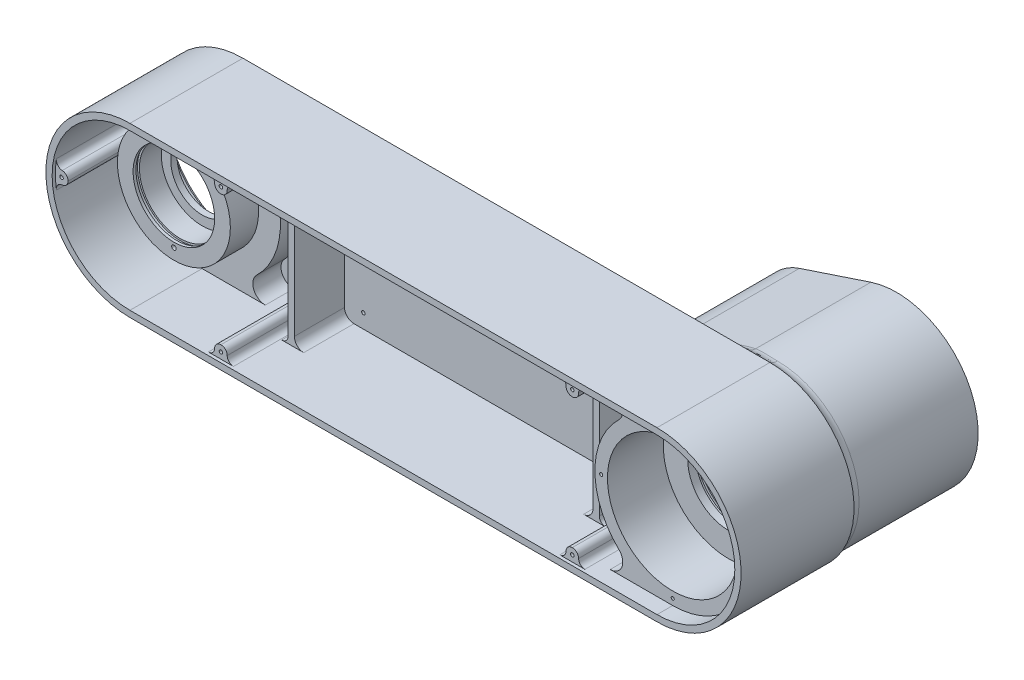
SolidWorks part; units mm, degrees
note: '?' marks a value the reader was unsure of. The reader was unsure of these and kept them because the rebuilt part matched: shared geometry of "Sketch1<2>", "Sketch5<2>", "Sketch20<2>".
ref_plane "Front Plane" through (0, 0, 0) normal (0, 0, 1) x (1, 0, 0)
ref_plane "Top Plane" through (0, 0, 0) normal (0, 1, 0) x (1, 0, 0)
ref_plane "Right Plane" through (0, 0, 0) normal (1, 0, 0) x (0, 0, -1)
sketch "Sketch1" plane through (0, 0, 0) normal (0, 0, 1) x (1, 0, 0)
  line L0 (0, 42.545) -> (266.7, 42.545)
  line L1 (0, -42.545) -> (266.7, -42.545)
  line L2 (0, 39.37) -> (266.7, 39.37)
  line L3 (0, -39.37) -> (266.7, -39.37)
  line L4 (266.7, 0) -> (0, 0) construction
  line L5 (133.35, 39.37) -> (133.35, -39.37) construction
  arc A0 (0, 42.545) -> (0, -42.545) centre (0, 0) ccw
  arc A1 (266.7, 42.545) -> (266.7, -42.545) centre (266.7, 0) cw
  arc A2 (266.7, 39.37) -> (266.7, -39.37) centre (266.7, 0) cw
  arc A3 (0, 39.37) -> (0, -39.37) centre (0, 0) ccw
  dimension "D1" = 85.09
  dimension "D2" = 266.7
  dimension "D3" = 3.175
extrude "Boss-Extrude1" add sketch "Sketch1" along normal blind 50.8
extrude "Boss-Extrude2" add sketch "Sketch1<2>" against normal blind 6.35 contours L2 A3 L3 A2 | A1 L0 A0 L1 A3 L2 A2 L3
sketch "Sketch1<2>" plane through (0, 0, 0) normal (0, 0, 1) x (1, 0, 0) same geometry as "Sketch1"
ref_plane "Plane1" through (0, 0, -6.35) normal (0, 0, -1) x (-1, 0, 0)
ref_plane "Plane2" through (0, 0, 0) normal (0, 0, 1) x (1, 0, 0)
sketch "Sketch3" plane through (0, 0, -6.35) normal (0, 0, -1) x (-1, 0, 0)
  circle A0 centre (0, 0) radius 38.1
  dimension "D1" = 76.2
extrude "Cut-Extrude1" cut sketch "Sketch3" against normal blind 5.08
ref_axis "Axis1" through (0, 0, -1.27) along (0, 0, -1)?
sketch "Sketch4" plane through (0, 0, 0) normal (0, 0, 1) x (1, 0, 0)
  circle A0 centre (0, 0) radius 31.75
  dimension "D1" = 63.5
extrude "Cut-Extrude2" cut sketch "Sketch4" against normal up to surface (6.35 mm away) contours A0 up to plane "Plane1"
ref_plane "Plane3" through (0, 0, 50.8) normal (0, 0, 1) x (1, 0, 0)
sketch "Sketch15" plane through (0, 0, 0) normal (0, 0, 1) x (1, 0, 0)
  circle A0 centre (0, 0) radius 31.75
  circle A1 centre (0, 0) radius 39.624
  arc A3 (0, 39.37) -> (0, -39.37) centre (0, 0) ccw construction
  dimension "D1" = 63.5
  dimension "D2" = 0.254
extrude "Boss-Extrude6" add sketch "Sketch15" along normal blind 11.0975
sketch "Sketch5" plane through (0, 0, -6.35) normal (0, 0, -1) x (-1, 0, 0)
  line L0 (0, 0) -> (-253.1261, -84.0003) construction
  line L1 (0, 0) -> (-266.7, 0) construction
  line L2 (-253.1261, -84.0003) -> (-266.7, 0) construction
  line L3 (-217.5391, -27.1742) -> (-253.6999, -39.1743)
  line L4 (-253.1261, 84.0003) -> (-266.7, 0) construction
  line L5 (-217.5391, 27.1742) -> (-253.6999, 39.1743)
  line L6 (0, 0) -> (-253.1261, 84.0003) construction
  line L7 (-218.5391, -24.1608) -> (-254.7, -36.1609)
  line L8 (-218.5391, 24.1608) -> (-254.7, 36.1609)
  arc A0 (-254.7, 36.1609) -> (-254.7, -36.1609) centre (-266.7, 0) ccw
  arc A2 (-253.6999, 39.1743) -> (-253.6999, -39.1743) centre (-266.7, 0) ccw
  arc A3 (-217.5391, -27.1742) -> (-217.5391, 27.1742) centre (-226.5569, 0) ccw
  arc A4 (-218.5391, -24.1608) -> (-218.5391, 24.1608) centre (-226.5569, 0) ccw
  dimension "D1" = 266.7
  dimension "D2" = 82.55
  dimension "D3" = 266.7
  dimension "D4" = 85.09
  dimension "D5" = 38.1
  dimension "D6" = 3.175
extrude "Boss-Extrude3" add sketch "Sketch5" along normal up to surface (64.07 mm away)
extrude "Boss-Extrude4" add sketch "Sketch5<2>" along normal up to surface (13.27 mm away) contours L7 A4 L8 A0
sketch "Sketch5<2>" plane through (0, 0, -6.35) normal (0, 0, -1) x (-1, 0, 0) same geometry as "Sketch5"
ref_plane "Plane4" through (0, 0, -19.62) normal (0, 0, -1) x (-1, 0, 0)
ref_axis "Axis5" through (266.7, 0, 50.8) along (0, 0, -1)?
sketch "Sketch20" plane through (0, 0, 0) normal (0, 0, 1) x (1, 0, 0)
  circle A0 centre (266.7, 0) radius 33.02
  circle A1 centre (266.7, 0) radius 39.37
  arc A2 (266.7, -39.37) -> (266.7, 39.37) centre (266.7, 0) ccw construction
  dimension "D1" = 6.35
extrude "Boss-Extrude9" add sketch "Sketch20" along normal blind 42.8625
extrude "Boss-Extrude10" add sketch "Sketch20<2>" along normal blind 14.59 contours A0
sketch "Sketch20<2>" plane through (0, 0, 0) normal (0, 0, 1) x (1, 0, 0) same geometry as "Sketch20"
sketch "Sketch23" plane through (0, 0, -19.62) normal (0, 0, -1) x (-1, 0, 0)
  circle A0 centre (-266.7, 0) radius 20.6375
  dimension "D1" = 41.275
extrude "Cut-Extrude6" cut sketch "Sketch23" against normal blind 28.575 from offset 6.35 offset against normal yes
sketch "Sketch24" plane through (0, 0, -19.62) normal (0, 0, -1) x (-1, 0, 0)
  circle A0 centre (-266.7, 0) radius 21.9075
  dimension "D1" = 43.815
extrude "Cut-Extrude7" cut sketch "Sketch24" against normal blind 1.7272 from offset 28.575 offset against normal yes
sketch "Sketch8" plane through (0, 0, 0) normal (0, 0, 1) x (1, 0, 0)
  circle A0 centre (266.7, 0) radius 14.2875
  arc A1 (266.7, -39.37) -> (266.7, 39.37) centre (266.7, 0) ccw construction
  dimension "D1" = 28.575
extrude "Cut-Extrude3" cut sketch "Sketch8" against normal up to surface (19.62 mm away) up to plane "Plane4"
ref_axis "Axis2" through (266.7, 0, -19.62) along (0, 0, 1)?
ref_axis "Axis3" through (266.7, 0, 0) along (-1, 0, 0)?
ref_axis "Axis4" through (133.35, 39.37, 0) along (0, -1, 0)?
sketch "Sketch9" plane through (0, 0, 0) normal (0, 0, 1) x (1, 0, 0)
  line L0 (64.135, 39.37) -> (202.565, 39.37)
  line L1 (202.565, 39.37) -> (202.565, 25.4)
  line L2 (202.565, 25.4) -> (64.135, 25.4)
  line L3 (64.135, 25.4) -> (64.135, 39.37)
  line L4 (64.135, -25.4) -> (64.135, -39.37)
  line L5 (64.135, -39.37) -> (202.565, -39.37)
  line L6 (202.565, -39.37) -> (202.565, -25.4)
  line L7 (202.565, -25.4) -> (64.135, -25.4)
  line L8 (64.135, 25.4) -> (64.135, 0) construction
  line L9 (202.565, 25.4) -> (202.565, -25.4) construction
  line L10 (64.135, 0) -> (64.135, -25.4) construction
  line L11 (266.7, 0) -> (0, 0) construction
  line L12 (133.35, 12.7) -> (133.35, -12.7) construction
  line L13 (133.35, 39.37) -> (133.35, -39.37) construction
  line L14 (64.135, 0) -> (0, 0) construction
  line L15 (202.565, 0) -> (266.7, 0) construction
  point P11 (199.39, 32.1818)
  point P16 (133.35, 0)
  point P20 (67.31, 32.1818)
  point P21 (67.31, -32.1818)
  point P22 (199.39, -32.1818)
  dimension "D1" = 78.74
  dimension "D2" = 25.4
  dimension "D3" = 3.175
  dimension "D4" = 138.43
  dimension "D5" = 25.4
  dimension "D6" = 32.1818
  dimension "D7" = 3.175
sketch "Sketch17" plane through (0, 0, 11.0975) normal (0, 0, 1) x (1, 0, 0)
  circle A0 centre (0, 0) radius 15.875
  circle A1 centre (0, 0) radius 39.624
  circle A2 centre (0, 0) radius 39.624 construction
  dimension "D1" = 31.75
extrude "Boss-Extrude7" add sketch "Sketch17" along normal blind 3.175
sketch "Sketch18" plane through (0, 0, 14.2725) normal (0, 0, 1) x (1, 0, 0)
  circle A0 centre (0, 0) radius 20.6375
  circle A1 centre (0, 0) radius 28.575
  dimension "D1" = 41.275
  dimension "D2" = 57.15
extrude "Boss-Extrude8" add sketch "Sketch18" along normal blind 14.2875
ref_plane "Plane7" through (0, 0, 14.2725) normal (0, 0, 1) x (1, 0, 0)
sketch "Sketch19" plane through (0, 0, 14.2725) normal (0, 0, 1) x (1, 0, 0)
  circle A0 centre (0, 0) radius 20.6375
  circle A1 centre (0, 0) radius 21.59
  dimension "D1" = 41.275
  dimension "D2" = 43.18
extrude "Cut-Extrude5" cut sketch "Sketch19" along normal blind 1.7272 from offset 11.1125
fillet "Fillet2" radius 6.35 2 edges at (4.4793, 39.37, 7.1363) (4.4793, -39.37, 7.1363)
sketch "Sketch25" plane through (0, 0, 42.8625) normal (0, 0, 1) x (1, 0, 0)
  line L0 (230.505, 0) -> (266.7, 0) construction
  circle A0 centre (230.505, 0) radius 0.7938
  circle A1 centre (266.7, 36.195) radius 0.7938
  circle A2 centre (302.895, 0) radius 0.7938
  circle A3 centre (266.7, -36.195) radius 0.7938
  point P13 (266.7, 0)
  dimension "D1" = 1.5875
  dimension "D2" = 36.195
  dimension "D3" = 4
extrude "Cut-Extrude8" cut sketch "Sketch25" against normal blind 12.7
sketch "Sketch27" plane through (0, 0, 28.56) normal (0, 0, 1) x (1, 0, 0)
  circle A0 centre (0, 0) radius 23.0124 construction
  point P3 (0, 23.0124)
  point P4 (0, -23.0124)
  dimension "D1" = 46.0248
hole_wizard "#4-40 Tapped Hole1" positions "Sketch29" profile "Sketch28" tap size "#4-40" standard "ANSI Inch"
sketch "Sketch29" plane through (0, 0, 28.56) normal (0, 0, 1) x (1, 0, 0)
  point P0 (0, 23.0124)
  point P3 (0, -23.0124)
sketch "Sketch28" plane through (0, 23.0124, 28.56) normal (1, 0, 0) x (0, -1, 0)
  line L0 (0, 0) -> (0, 8.9342)
  line L1 (0, 8.9342) -> (1.1303, 8.255)
  line L2 (1.1303, 8.255) -> (1.1303, 0)
  line L5 (1.1303, 0) -> (0, 0)
  line L10 (0, 8.9342) -> (-1.1303, 8.255) construction
  line L11 (0, -6.35) -> (0, 107.95) construction
  dimension "Tap Drill Dia." = 2.2606
  dimension "Tap Drill Depth" = 8.255
  dimension "Drill Angle" = 118
cosmetic thread "Hole Thread16" parameters "D1"=6.35, "D2"=2.8448
cosmetic thread "Hole Thread17" parameters "D1"=6.35, "D2"=2.8448
sketch "Sketch30" plane through (0, 0, -19.62) normal (0, 0, -1) x (-1, 0, 0)
  circle A0 centre (-266.7, 0) radius 23.0124 construction
  point P2 (-266.7, -23.0124)
  point P4 (-266.7, 23.0124)
  dimension "D1" = 46.0248
hole_wizard "#4-40 Tapped Hole2" positions "Sketch32" profile "Sketch31" tap size "#4-40" standard "ANSI Inch"
sketch "Sketch32" plane through (0, 0, -19.62) normal (0, 0, -1) x (-1, 0, 0)
  point P0 (-266.7, -23.0124)
  point P3 (-266.7, 23.0124)
sketch "Sketch31" plane through (266.7, -23.0124, -19.62) normal (1, 0, 0) x (0, 1, 0)
  line L0 (0, 0) -> (0, 8.9342)
  line L1 (0, 8.9342) -> (1.1303, 8.255)
  line L2 (1.1303, 8.255) -> (1.1303, 0)
  line L5 (1.1303, 0) -> (0, 0)
  line L10 (0, 8.9342) -> (-1.1303, 8.255) construction
  line L11 (0, -6.35) -> (0, 107.95) construction
  dimension "Tap Drill Dia." = 2.2606
  dimension "Tap Drill Depth" = 8.255
  dimension "Drill Angle" = 118
cosmetic thread "Hole Thread18" parameters "D1"=6.35, "D2"=2.8448
cosmetic thread "Hole Thread19" parameters "D1"=6.35, "D2"=2.8448
fillet "Fillet3" radius 6.35 2 edges at (266.7, 39.37, 21.4312) (266.7, -39.37, 21.4312)
sketch "Sketch33" plane through (0, 0, 0) normal (0, 0, 1) x (1, 0, 0)
  line L0 (47.625, -39.37) -> (47.625, -33.02)
  line L1 (31.9889, -39.37) -> (235.0773, -39.37) construction
  line L2 (47.625, -33.02) -> (41.275, -33.02)
  line L3 (41.275, -33.02) -> (41.275, -39.37)
  line L4 (41.275, -39.37) -> (47.625, -39.37)
  line L5 (44.45, -39.37) -> (44.45, -33.02) construction
  line L6 (225.425, -39.37) -> (225.425, -33.02)
  line L7 (31.9889, -39.37) -> (235.0773, -39.37) construction
  line L8 (225.425, -33.02) -> (219.075, -33.02)
  line L9 (219.075, -33.02) -> (219.075, -39.37)
  line L10 (219.075, -39.37) -> (225.425, -39.37)
  line L11 (222.25, -39.37) -> (222.25, -33.02) construction
  line L12 (-39.2418, -3.175) -> (-32.8918, -3.175)
  line L14 (-32.8918, -3.175) -> (-32.8918, 3.175)
  line L15 (-32.8918, 3.175) -> (-39.2418, 3.175)
  line L16 (-32.8918, 0) -> (-39.37, 0) construction
  line L17 (0, 0) -> (266.7, 0) construction
  line L18 (47.625, 39.37) -> (47.625, 33.02)
  line L19 (41.275, 39.37) -> (47.625, 39.37)
  line L20 (41.275, 33.02) -> (41.275, 39.37)
  line L21 (47.625, 33.02) -> (41.275, 33.02)
  line L22 (219.075, 39.37) -> (225.425, 39.37)
  line L23 (219.075, 33.02) -> (219.075, 39.37)
  line L24 (225.425, 33.02) -> (219.075, 33.02)
  line L25 (225.425, 39.37) -> (225.425, 33.02)
  arc A0 (0, 39.37) -> (0, -39.37) centre (0, 0) ccw construction
  arc A1 (-39.2418, 3.175) -> (-39.2418, -3.175) centre (0, 0) ccw
  point P16 (222.25, -36.195)
  point P17 (44.45, -36.195)
  point P29 (44.45, 36.195)
  point P36 (222.25, 36.195)
  point P41 (-36.195, 0)
  dimension "D1" = 6.35
  dimension "D2" = 6.35
  dimension "D3" = 44.45
  dimension "D4" = 44.45
  dimension "D5" = 6.35
  dimension "D6" = 6.35
  dimension "D7" = 6.35
  dimension "D8" = 6.35
  dimension "D9" = 3.175
extrude "Boss-Extrude11" add sketch "Sketch33" along normal offset from surface (49.2125 mm away) 1.5875 up to face at (133.35, 0, 50.8)
fillet "Fillet4" radius 3.175 18 edges at (219.075, 39.37, 24.6062) (225.425, 39.37, 24.6062) (225.425, 33.02, 24.6062) (219.075, 33.02, 24.6062) (41.275, 39.37, 24.6062) (41.275, 33.02, 24.6062) (47.625, 33.02, 24.6062) (47.625, 39.37, 24.6062) (-32.8918, 3.175, 31.7425) (-32.8918, -3.175, 31.7425) (41.275, -39.37, 24.6062) (41.275, -33.02, 24.6062) (47.625, -33.02, 24.6062) (47.625, -39.37, 24.6062) (219.075, -39.37, 24.6062) (219.075, -33.02, 24.6062) (225.425, -33.02, 24.6062) (225.425, -39.37, 24.6062)
fillet "Fillet5" radius 3.175 2 edges at (-39.2418, -3.175, 31.7425) (-39.2418, 3.175, 31.7425)
ref_plane "Plane8" through (0, 0, 49.2125) normal (0, 0, 1) x (1, 0, 0)
hole_wizard "#2-56 Tapped Hole3" positions "Sketch37" profile "Sketch36" tap size "#2-56" standard "ANSI Inch"
sketch "Sketch37" plane through (0, 0, 49.2125) normal (0, 0, 1) x (1, 0, 0)
  point P0 (222.25, -36.195)
  point P3 (44.45, -36.195)
  point P6 (44.45, 36.195)
  point P8 (-36.195, 0)
  point P11 (222.25, 36.195)
sketch "Sketch36" plane through (222.25, -36.195, 49.2125) normal (1, 0, 0) x (0, -1, 0)
  line L0 (0, 0) -> (0, 13.2342)
  line L1 (0, 13.2342) -> (0.889, 12.7)
  line L2 (0.889, 12.7) -> (0.889, 0)
  line L5 (0.889, 0) -> (0, 0)
  line L10 (0, 13.2342) -> (-0.889, 12.7) construction
  line L11 (0, -6.35) -> (0, 107.95) construction
  dimension "Tap Drill Dia." = 1.778
  dimension "Tap Drill Depth" = 12.7
  dimension "Drill Angle" = 118
cosmetic thread "Hole Thread20" parameters "D1"=11.43, "D2"=2.1844
cosmetic thread "Hole Thread21" parameters "D1"=11.43, "D2"=2.1844
cosmetic thread "Hole Thread22" parameters "D1"=11.43, "D2"=2.1844
cosmetic thread "Hole Thread23" parameters "D1"=11.43, "D2"=2.1844
cosmetic thread "Hole Thread24" parameters "D1"=11.43, "D2"=2.1844
sketch "Sketch38" plane through (0, 0, 0) normal (0, 0, 1) x (1, 0, 0)
  line L0 (217.5391, 27.1742) -> (253.6999, 39.1743) construction
  line L1 (253.6999, -39.1743) -> (217.5391, -27.1742) construction
  line L2 (217.5391, 27.1742) -> (253.6999, 39.1743) construction
  line L3 (253.6999, -39.1743) -> (217.5391, -27.1742) construction
  line L4 (226.5569, 0) -> (226.5569, -12.7564)
  line L5 (226.5569, 0) -> (226.5569, 12.7564)
  line L6 (226.5569, 0) -> (213.8004, 0) construction
  arc A0 (217.5391, 27.1742) -> (217.5391, -27.1742) centre (226.5569, 0) ccw construction
  arc A1 (253.6999, -39.1743) -> (253.6999, 39.1743) centre (266.7, 0) ccw construction
  arc A2 (217.5391, 27.1742) -> (217.5391, -27.1742) centre (226.5569, 0) ccw construction
  arc A3 (253.6999, -39.1743) -> (253.6999, 39.1743) centre (266.7, 0) ccw construction
  arc A4 (226.5569, 12.7564) -> (226.5569, -12.7564) centre (226.5569, 0) ccw
  dimension "D1" = 15.875
  dimension "D3" = 180
extrude "Cut-Extrude9" cut sketch "Sketch38" against normal up to surface (19.62 mm away)
fillet "Fillet6" radius 3.175 2 edges at (226.5569, 12.7564, -9.81) (226.5569, -12.7564, -9.81)
fillet "Fillet7" radius 3.175 4 edges at (225.2177, 11.6306, -19.62) (225.2177, -11.6306, -19.62) (226.5569, 0, -19.62) (213.8004, 0, -19.62)
fillet "Fillet8" radius 6.35 3 edges at (235.6195, 33.1743, -6.35) (197.9254, 0, -6.35) (235.6195, -33.1743, -6.35)
sketch "Sketch39" plane through (0, 0, -1.27) normal (0, 0, -1) x (-1, 0, 0)
  circle A0 centre (0, 0) radius 34.29 construction
  point P3 (0, 34.29)
  point P4 (-34.29, 0)
  point P5 (0, -34.29)
  point P6 (34.29, 0)
  dimension "D1" = 68.58
hole_wizard "#8-32 Tapped Hole1" positions "Sketch41" profile "Sketch40" tap size "#8-32" standard "ANSI Inch"
sketch "Sketch41" plane through (0, 0, -1.27) normal (0, 0, -1) x (-1, 0, 0)
  point P0 (0, 34.29)
  point P3 (-34.29, 0)
  point P6 (0, -34.29)
  point P9 (34.29, 0)
sketch "Sketch40" plane through (0, 34.29, -1.27) normal (1, 0, 0) x (0, 1, 0)
  line L0 (0, 0) -> (0, 13.4043)
  line L1 (0, 13.4043) -> (1.7272, 12.3665)
  line L2 (1.7272, 12.3665) -> (1.7272, 0)
  line L5 (1.7272, 0) -> (0, 0)
  line L10 (0, 13.4043) -> (-1.7272, 12.3665) construction
  line L11 (0, -6.35) -> (0, 107.95) construction
  dimension "Tap Drill Dia." = 3.4544
  dimension "Tap Drill Depth" = 12.3665
  dimension "Drill Angle" = 118
cosmetic thread "Hole Thread25" parameters "D1"=10.16, "D2"=4.1656
cosmetic thread "Hole Thread26" parameters "D1"=10.16, "D2"=4.1656
cosmetic thread "Hole Thread27" parameters "D1"=10.16, "D2"=4.1656
cosmetic thread "Hole Thread28" parameters "D1"=10.16, "D2"=4.1656
sketch "Sketch42" plane through (0, 0, -19.62) normal (0, 0, -1) x (-1, 0, 0)
  line L0 (-201.1004, 3.175) -> (-207.4504, 3.175)
  line L1 (-207.4504, 3.175) -> (-207.4504, -3.175)
  line L2 (-207.4504, -3.175) -> (-201.1004, -3.175)
  line L3 (-201.1004, -3.175) -> (-201.1004, 3.175)
  line L4 (-201.1004, 0) -> (-207.4504, 0) construction
  line L5 (-243.3134, 32.3822) -> (-245.3134, 26.3554)
  line L6 (-218.5391, 24.1608) -> (-254.7, 36.1609) construction
  line L7 (-245.3134, 26.3554) -> (-239.2866, 24.3554)
  line L8 (-239.2866, 24.3554) -> (-237.2866, 30.3822)
  line L9 (-237.2866, 30.3822) -> (-243.3134, 32.3822)
  line L10 (-240.3, 31.3822) -> (-242.3, 25.3554) construction
  line L11 (-240.3, -31.3822) -> (-242.3, -25.3554) construction
  line L12 (-239.2866, -24.3554) -> (-237.2866, -30.3822)
  line L13 (-237.2866, -30.3822) -> (-243.3134, -32.3822)
  line L14 (-243.3134, -32.3822) -> (-245.3134, -26.3554)
  line L15 (-245.3134, -26.3554) -> (-239.2866, -24.3554)
  line L16 (-298.45, 0) -> (-304.8, 0) construction
  line L17 (-304.8, 3.175) -> (-298.45, 3.175)
  line L18 (-304.8, 3.175) -> (-304.8, -3.175)
  line L19 (-304.8, -3.175) -> (-298.45, -3.175)
  line L20 (-298.45, 3.175) -> (-298.45, -3.175)
  arc A0 (-218.5391, -24.1608) -> (-218.5391, 24.1608) centre (-226.5569, 0) ccw construction
  arc A2 (-254.7, 36.1609) -> (-254.7, -36.1609) centre (-266.7, 0) ccw construction
  point P10 (-204.2754, 0)
  point P20 (-241.3, 28.3688)
  point P21 (-241.3, -28.3688)
  point P37 (-301.625, 0)
  dimension "D1" = 6.35
  dimension "D2" = 6.35
  dimension "D3" = 3.175
  dimension "D4" = 6.35
  dimension "D5" = 6.35
  dimension "D6" = 25.4
  dimension "D7" = 6.35
  dimension "D8" = 6.35
  dimension "D9" = 3.175
extrude "Boss-Extrude12" add sketch "Sketch42" along normal offset from surface (49.2125 mm away) 1.5875 up to face at (244.7849, 0, -70.42)
fillet "Fillet9" radius 3.175 12 edges at (237.2866, -30.3822, -44.2262) (239.2866, -24.3554, -44.2262) (245.3134, -26.3554, -44.2262) (243.3134, -32.3822, -44.2262) (298.45, 3.175, -44.2262) (298.45, -3.175, -44.2262) (237.2866, 30.3822, -44.2262) (243.3134, 32.3822, -44.2262) (239.2866, 24.3554, -44.2262) (245.3134, 26.3554, -44.2262) (207.4504, -3.175, -44.2262) (207.4504, 3.175, -44.2262)
fillet "Fillet10" radius 3.175 4 edges at (304.6675, 3.175, -44.2262) (304.6675, -3.175, -44.2262) (201.2992, -3.175, -44.2262) (201.2992, 3.175, -44.2262)
ref_plane "Plane9" through (0, 0, -68.8325) normal (0, 0, -1) x (-1, 0, 0)
hole_wizard "#2-56 Tapped Hole4" positions "Sketch46" profile "Sketch45" tap size "#2-56" standard "ANSI Inch"
sketch "Sketch46" plane through (0, 0, -68.8325) normal (0, 0, -1) x (-1, 0, 0)
  point P0 (-204.2754, 0)
  point P2 (-241.3, 28.3688)
  point P4 (-301.625, 0)
  point P6 (-241.3, -28.3688)
sketch "Sketch45" plane through (204.2754, 0, -68.8325) normal (1, 0, 0) x (0, 1, 0)
  line L0 (0, 0) -> (0, 8.4082)
  line L1 (0, 8.4082) -> (0.889, 7.874)
  line L2 (0.889, 7.874) -> (0.889, 0)
  line L5 (0.889, 0) -> (0, 0)
  line L10 (0, 8.4082) -> (-0.889, 7.874) construction
  line L11 (0, -6.35) -> (0, 107.95) construction
  dimension "Tap Drill Dia." = 1.778
  dimension "Tap Drill Depth" = 7.874
  dimension "Drill Angle" = 118
cosmetic thread "Hole Thread29" parameters "D1"=6.35, "D2"=2.1844
cosmetic thread "Hole Thread30" parameters "D1"=6.35, "D2"=2.1844
cosmetic thread "Hole Thread31" parameters "D1"=6.35, "D2"=2.1844
cosmetic thread "Hole Thread32" parameters "D1"=6.35, "D2"=2.1844
hole_wizard "#2-56 Tapped Hole5" positions "Sketch48" profile "Sketch47" tap size "#2-56" standard "ANSI Inch"
sketch "Sketch48" plane through (0, 0, 0) normal (0, 0, 1) x (1, 0, 0)
  point P0 (199.39, -32.1818)
  point P3 (199.39, 32.1818)
  point P6 (67.31, 32.1818)
  point P9 (67.31, -32.1818)
sketch "Sketch47" plane through (199.39, -32.1818, 0) normal (1, 0, 0) x (0, -1, 0)
  line L0 (0, 0) -> (0, 3.7092)
  line L1 (0, 3.7092) -> (0.889, 3.175)
  line L2 (0.889, 3.175) -> (0.889, 0)
  line L5 (0.889, 0) -> (0, 0)
  line L10 (0, 3.7092) -> (-0.889, 3.175) construction
  line L11 (0, -6.35) -> (0, 107.95) construction
  dimension "Tap Drill Dia." = 1.778
  dimension "Tap Drill Depth" = 3.175
  dimension "Drill Angle" = 118
cosmetic thread "Hole Thread33" parameters "D1"=3.175, "D2"=2.1844
cosmetic thread "Hole Thread34" parameters "D1"=3.175, "D2"=2.1844
cosmetic thread "Hole Thread35" parameters "D1"=3.175, "D2"=2.1844
cosmetic thread "Hole Thread36" parameters "D1"=3.175, "D2"=2.1844
sketch "Sketch49" plane through (0, 0, 0) normal (0, 0, 1) x (1, 0, 0)
  line L0 (215.9, 39.37) -> (50.8, 39.37) construction
  line L1 (54.61, 39.37) -> (57.785, 39.37)
  line L2 (54.61, 39.37) -> (54.61, -39.37)
  line L3 (54.61, -39.37) -> (57.785, -39.37)
  line L4 (57.785, 39.37) -> (57.785, -39.37)
  line L5 (50.8, -39.37) -> (215.9, -39.37) construction
  line L6 (266.7, 39.37) -> (0, 39.37) construction
  line L7 (208.915, 39.37) -> (212.09, 39.37)
  line L8 (208.915, 39.37) -> (208.915, -39.37)
  line L9 (208.915, -39.37) -> (212.09, -39.37)
  line L10 (212.09, 39.37) -> (212.09, -39.37)
  dimension "D1" = 3.175
  dimension "D2" = 9.525
  dimension "D3" = 3.175
  dimension "D4" = 9.525
extrude "Boss-Extrude13" add sketch "Sketch49" along normal blind 25.4
fillet "Fillet11" radius 3.175 3 edges at (225.2177, 11.6306, 0) (225.2177, -11.6306, 0) (213.8004, 0, 0)
fillet "Fillet13" radius 3.175 4 edges at (212.09, 39.37, 12.7) (212.09, -39.37, 12.7) (54.61, -39.37, 12.7) (54.61, 39.37, 12.7)
fillet "Fillet14" radius 4.7625 4 edges at (208.915, 39.37, 12.7) (208.915, -39.37, 12.7) (57.785, -39.37, 12.7) (57.785, 39.37, 12.7)
equation "\"D1@Sketch9\"= \"D1@Sketch1\" - 2 * \"D3@Sketch1\""
equation "\"D1@Boss-Extrude6\"=.61191in - .05in - .125"
equation "\"D1@Boss-Extrude8\"=7/16 + .125 "
